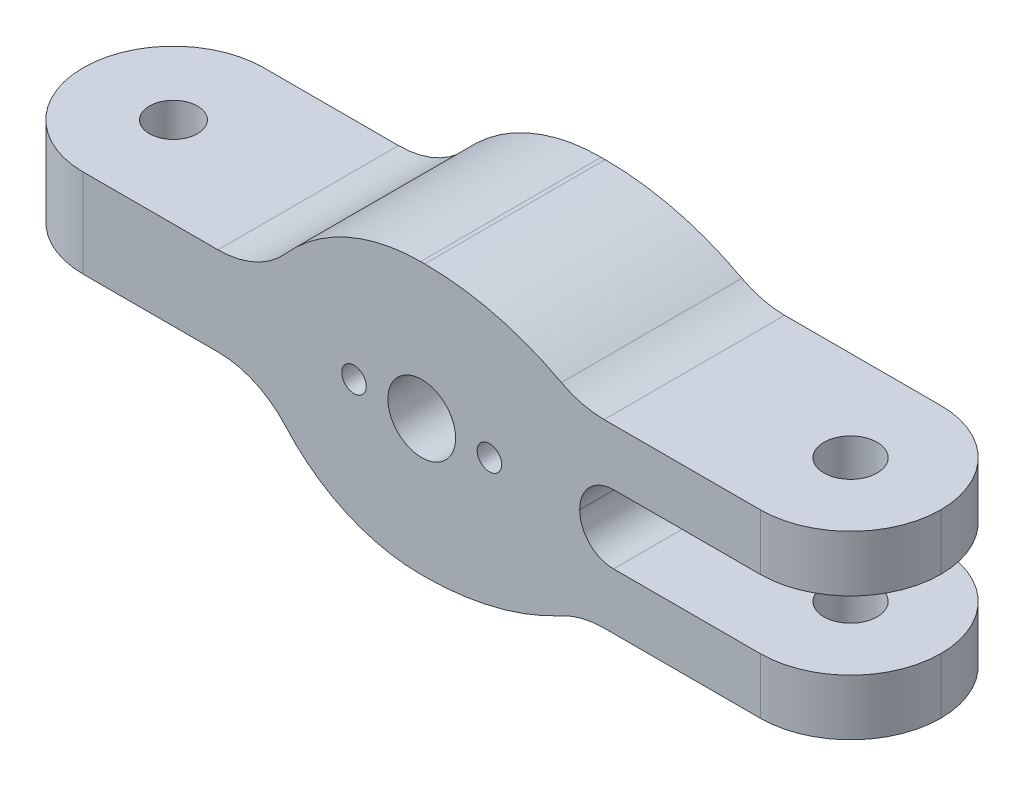
SolidWorks part; units mm, degrees
ref_plane "Front Plane" through (0, 0, 0) normal (0, 0, 1) x (1, 0, 0)
ref_plane "Top Plane" through (0, 0, 0) normal (0, 1, 0) x (1, 0, 0)
ref_plane "Right Plane" through (0, 0, 0) normal (1, 0, 0) x (0, 0, -1)
sketch "Sketch1" plane through (0, 0, 0) normal (0, 0, 1) x (1, 0, 0)
  line L1 (-60.325, -19.05) -> (60.325, -19.05)
  line L2 (-60.325, -19.05) -> (-60.325, 19.05)
  line L3 (-60.325, 19.05) -> (60.325, 19.05)
  line L4 (60.325, -19.05) -> (60.325, 19.05)
  line L5 (-60.325, -19.05) -> (60.325, 19.05) construction
  line L6 (-60.325, 19.05) -> (60.325, -19.05) construction
  point P0 (0, 0)
  dimension "D1" = 120.65
  dimension "D2" = 38.1
extrude "Boss-Extrude1" add sketch "Sketch1" along normal mid plane 25.4
sketch "Sketch2" plane through (0, 0, -12.7) normal (0, 0, -1) x (-1, 0, 0)
  circle A0 centre (0, 0) radius 14.351
  dimension "D1" = 28.702
extrude "Cut-Extrude1" cut sketch "Sketch2" against normal blind 12.7
hole_wizard "#8-32 Tapped Hole1" positions "Sketch4" profile "Sketch6" tap size "#8-32" standard "ANSI Inch"
sketch "Sketch4" plane through (0, 0, 12.7) normal (0, 0, 1) x (1, 0, 0)
  circle A0 centre (9.525, 0) radius 1.5875 construction
  circle A1 centre (-9.525, 0) radius 1.5875 construction
  point P0 (9.525, 0)
  point P2 (-9.525, 0)
cosmetic thread "Hole Thread1" parameters "D1"=8.331, "D2"=4.1656
cosmetic thread "Hole Thread2" parameters "D1"=8.331, "D2"=4.1656
sketch "Sketch6" plane through (9.525, 0, 12.7) normal (1, 0, 0) x (0, -1, 0)
  line L0 (0, 0) -> (0, 13.7378)
  line L1 (0, 13.7378) -> (1.7272, 12.7)
  line L2 (1.7272, 12.7) -> (1.7272, 0)
  line L5 (1.7272, 0) -> (0, 0)
  line L10 (0, 13.7378) -> (-1.7272, 12.7) construction
  line L11 (0, -6.35) -> (0, 107.95) construction
  dimension "Tap Drill Dia." = 3.4544
  dimension "Tap Drill Depth" = 12.7
  dimension "Drill Angle" = 118
sketch "Sketch7" plane through (0, 0, 12.7) normal (0, 0, 1) x (1, 0, 0)
  circle A0 centre (0, 0) radius 4.7625
  dimension "D1" = 9.525
extrude "Cut-Extrude2" cut sketch "Sketch7" against normal up to next
fillet "Fillet1" radius 12.7 4 edges at (-60.325, 0, 12.7) (-60.325, 0, -12.7) (60.325, 0, 12.7) (60.325, 0, -12.7)
sketch "Sketch12" plane through (0, 0, 12.7) normal (0, 0, 1) x (1, 0, 0)
  line L0 (60.325, -19.05) -> (60.325, 19.05) construction
  line L1 (-60.325, 19.05) -> (-22.225, 19.05)
  line L2 (-60.325, 19.05) -> (-60.325, 6.223)
  line L3 (-60.325, 6.223) -> (-22.225, 6.223)
  line L4 (-22.225, 19.05) -> (-22.225, 6.223)
  line L5 (22.225, 4.826) -> (60.325, 4.826)
  line L6 (22.225, 4.826) -> (22.225, -4.826)
  line L7 (22.225, -4.826) -> (60.325, -4.826)
  line L8 (60.325, 4.826) -> (60.325, -4.826)
  line L9 (-38.1, 6.223) -> (-57.15, 6.223) construction
  line L10 (-60.325, -19.05) -> (-22.225, -19.05)
  line L11 (-60.325, -19.05) -> (-60.325, -6.223)
  line L12 (-60.325, -6.223) -> (-22.225, -6.223)
  line L13 (-22.225, -19.05) -> (-22.225, -6.223)
  line L14 (-38.1, -6.223) -> (-57.15, -6.223) construction
  line L15 (47.625, 19.05) -> (-47.625, 19.05) construction
  line L16 (22.225, 0) -> (60.325, 0) construction
  line L17 (41.5758, 0) -> (53.6742, 0) construction
  line L18 (22.225, 19.05) -> (60.325, 19.05)
  line L19 (22.225, 19.05) -> (22.225, 12.7)
  line L20 (22.225, 12.7) -> (60.325, 12.7)
  line L21 (60.325, 19.05) -> (60.325, 12.7)
  line L22 (-47.625, -19.05) -> (47.625, -19.05) construction
  line L23 (22.225, -19.05) -> (60.325, -19.05)
  line L24 (22.225, -19.05) -> (22.225, -12.7)
  line L25 (22.225, -12.7) -> (60.325, -12.7)
  line L26 (60.325, -19.05) -> (60.325, -12.7)
  dimension "D1" = 38.1
  dimension "D4" = 38.1
  dimension "D5" = 9.652
  dimension "D2" = 6.35
  dimension "D3" = 6.35
extrude "Cut-Extrude6" cut sketch "Sketch12" against normal through all
sketch "Sketch13" plane through (0, 19.05, 0) normal (0, 1, 0) x (1, 0, 0)
  circle A0 centre (47.625, 0) radius 3.7465
  circle A1 centre (47.625, 0) radius 3.4925 construction
  circle A2 centre (47.625, 0) radius 3.4925 construction
  dimension "D1" = 0.254
extrude "Cut-Extrude7" cut sketch "Sketch13" against normal through all contours A0
hole_wizard "1/4 Clearance Hole1" positions "Sketch14" profile "Sketch15" hole size "1/4" standard "ANSI Inch"
sketch "Sketch14" plane through (0, 9.525, -30.5975) normal (0, 1, 0) x (0, 0, 1)
  line L0 (30.5975, -47.625) -> (81.3975, -47.625) construction
  line L1 (196.3325, 47.625) -> (196.3325, -47.625) construction
  point P0 (30.5975, -47.625)
  point P3 (62.3475, -47.625)
  point P5 (81.3975, -47.625)
  point P15 (196.3325, -47.625)
sketch "Sketch15" plane through (-47.625, 9.525, 0) normal (1, 0, 0) x (0, 0, 1)
  line L0 (0, 0) -> (0, 21.0798)
  line L1 (0, 21.0798) -> (3.3782, 19.05)
  line L2 (3.3782, 19.05) -> (3.3782, 0)
  line L3 (3.3782, 0) -> (0, 0)
  line L4 (0, 21.0798) -> (-3.3782, 19.05) construction
  line L5 (0, -6.35) -> (0, 107.95) construction
  dimension "Hole Dia." = 6.7564
  dimension "Hole Depth" = 19.05
  dimension "Drill Angle" = 118
chamfer "Chamfer1" distance 2.54 angle 45 1 edges at (-4.7625, 0, 0)
fillet "Fillet2" radius 25.4 2 edges at (-22.225, -19.05, 0) (-22.225, 19.05, 0)
fillet "Fillet3" radius 12.7 2 edges at (-22.225, -6.223, 0) (-22.225, 6.223, 0)
fillet "Fillet4" radius 40.64 2 edges at (22.225, -19.05, 0) (22.225, 19.05, 0)
fillet "Fillet5" radius 12.7 2 edges at (22.225, -12.7, 0) (22.225, 12.7, 0)
fillet "Fillet6" radius 4.7625 2 edges at (22.225, -4.826, 0) (22.225, 4.826, 0)
equation "\"D3@Sketch12\"=\"D2@Sketch12\""
